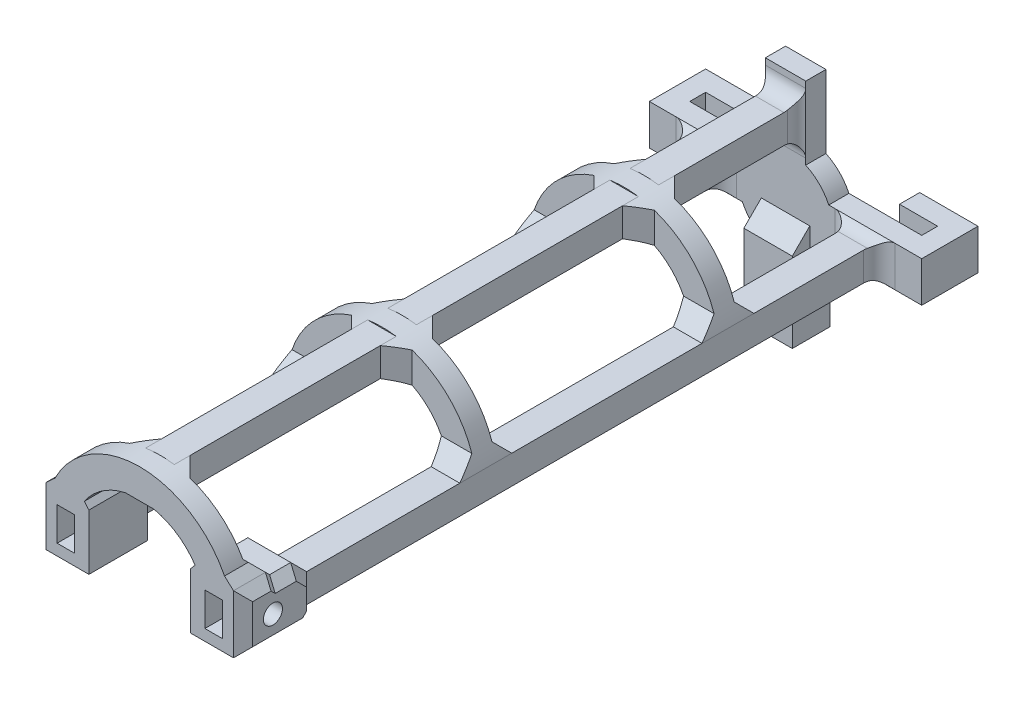
SolidWorks part; units mm, degrees
note: The reader was unsure of these and kept them because the rebuilt part matched: shared geometry of "Sketch11<2>", "Sketch11<3>", "Sketch15<2>", "Sketch14<2>".
ref_plane "Front Plane" through (0, 0, 0) normal (0, 0, 1) x (1, 0, 0)
ref_plane "Top Plane" through (0, 0, 0) normal (0, 1, 0) x (1, 0, 0)
ref_plane "Right Plane" through (0, 0, 0) normal (1, 0, 0) x (0, 0, -1)
sketch "Sketch1" plane through (0, 0, 0) normal (0, 0, 1) x (1, 0, 0)
  line L0 (-13.5896, -6.35) -> (-36.5, -6.35)
  line L1 (-6.35, 36.5) -> (6.35, 36.5)
  line L2 (-6.35, 36.5) -> (-6.35, 13.5896)
  line L3 (-7.62, -33) -> (7.62, -33)
  line L4 (6.35, 36.5) -> (6.35, 13.5896)
  line L5 (36.5, 6.35) -> (13.5896, 6.35)
  line L6 (36.5, 6.35) -> (36.5, -6.35)
  line L7 (36.5, -6.35) -> (13.5896, -6.35)
  line L8 (-36.5, 6.35) -> (-36.5, -6.35)
  line L9 (7.62, -12.9204) -> (7.62, -33)
  line L10 (-13.5896, 6.35) -> (-36.5, 6.35)
  line L11 (-7.62, -12.9204) -> (-7.62, -33)
  arc A0 (-13.5896, -6.35) -> (-7.62, -12.9204) centre (0, 0) ccw
  arc A1 (-6.35, 13.5896) -> (-13.5896, 6.35) centre (0, 0) ccw
  arc A2 (13.5896, 6.35) -> (6.35, 13.5896) centre (0, 0) ccw
  arc A3 (7.62, -12.9204) -> (13.5896, -6.35) centre (0, 0) ccw
  point P1 (6.35, -38.6284)
  point P11 (0, 36.5)
  point P13 (-36.5, 0)
  point P16 (6.3526, -42.9555)
  point P22 (9.9826, 34.5862)
  point P23 (-35.5946, -4.6384)
  dimension "D3" = 15
  dimension "D1" = 73
  dimension "D2" = 12.7
  dimension "D4" = 15.24
  dimension "D5" = 33
extrude "Boss-Extrude1" add sketch "Sketch1" along normal blind 6.35
sketch "Sketch5" plane through (7.62, 0, 0) normal (1, 0, 0) x (0, 0, -1)
  line L0 (-6.35, -2.325) -> (-11.85, -7.825)
  line L1 (-6.35, -33) -> (-11.85, -33)
  line L2 (-6.35, -33) -> (-6.35, -2.325)
  line L4 (-11.85, -33) -> (-11.85, -7.825)
  line L5 (0, -33) -> (0, -12.9204) construction
  point P7 (-11.85, -19.083)
  dimension "D1" = 135
  dimension "D2" = 11.85
  dimension "D3" = 25.175
extrude "Boss-Extrude2" add sketch "Sketch5" against normal up to surface (15.24 mm away) up to face at (-7.62, -22.9602, 3.175)
sketch "Sketch9" plane through (0, 6.35, 0) normal (0, 1, 0) x (1, 0, 0)
  line L0 (-36.5, -6.35) -> (-42.85, -6.35)
  line L1 (-42.85, -6.35) -> (-42.85, 11.35)
  line L2 (-42.85, 11.35) -> (-24.5, 11.35)
  line L9 (-36.5, 0) -> (-36.5, 5)
  line L10 (-36.5, 5) -> (-24.5, 5)
  line L11 (-24.5, 5) -> (-24.5, 11.35)
  line L12 (-36.5, 0) -> (-36.5, -6.35)
  line L14 (0, 0) -> (0, 11.35) construction
  line L15 (36.5, 0) -> (36.5, -6.35)
  line L16 (24.5, 5) -> (24.5, 11.35)
  line L17 (36.5, 5) -> (24.5, 5)
  line L18 (36.5, 0) -> (36.5, 5)
  line L19 (42.85, 11.35) -> (24.5, 11.35)
  line L20 (42.85, -6.35) -> (42.85, 11.35)
  line L21 (36.5, -6.35) -> (42.85, -6.35)
  dimension "D1" = 5
  dimension "D2" = 12
  dimension "D3" = 6.35
  dimension "D4" = 6.35
extrude "Boss-Extrude4" add sketch "Sketch9" against normal up to surface (12.7 mm away) up to face at (-25.0448, -6.35, 3.175)
sketch "Sketch6" plane through (0, -33, 0) normal (0, -1, 0) x (1, 0, 0)
  line L0 (-7.62, 11.85) -> (-7.62, 0) construction
  line L1 (-5.25, 8.675) -> (5.25, 8.675)
  line L2 (-5.25, 8.675) -> (-5.25, 3.175)
  line L3 (-5.25, 3.175) -> (5.25, 3.175)
  line L4 (5.25, 8.675) -> (5.25, 3.175)
  point P4 (0, 3.175)
  point P8 (-7.62, 5.925)
  point P9 (-5.25, 5.925)
  dimension "D1" = 10.5
  dimension "D2" = 5.5
extrude "Cut-Extrude1" cut sketch "Sketch6" against normal blind 22
chamfer "Chamfer2" distance 0.6 angle 45 4 edges at (-5.25, -22, 3.175) (-5.25, -22, 8.675) (5.25, -22, 8.675) (5.25, -22, 3.175)
sketch "Sketch7" plane through (0, 0, 6.35) normal (0, 0, 1) x (1, 0, 0)
  line L0 (0, 0) -> (0, 25) construction
  line L1 (-25, 0) -> (0, 0) construction
  line L2 (0, 0) -> (25, 0) construction
  line L4 (-29.5, -4.5) -> (-20.5, -4.5)
  line L5 (-29.5, -4.5) -> (-29.5, 4.5)
  line L6 (-29.5, 4.5) -> (-20.5, 4.5)
  line L7 (-20.5, -4.5) -> (-20.5, 4.5)
  line L8 (-29.5, -4.5) -> (-20.5, 4.5) construction
  line L9 (-29.5, 4.5) -> (-20.5, -4.5) construction
  line L10 (-4.5, 29.5) -> (4.5, 29.5)
  line L11 (-4.5, 29.5) -> (-4.5, 20.5)
  line L12 (-4.5, 20.5) -> (4.5, 20.5)
  line L13 (4.5, 29.5) -> (4.5, 20.5)
  line L14 (-4.5, 29.5) -> (4.5, 20.5) construction
  line L15 (-4.5, 20.5) -> (4.5, 29.5) construction
  line L16 (20.5, 4.5) -> (29.5, 4.5)
  line L17 (20.5, 4.5) -> (20.5, -4.5)
  line L18 (20.5, -4.5) -> (29.5, -4.5)
  line L19 (29.5, 4.5) -> (29.5, -4.5)
  line L20 (20.5, 4.5) -> (29.5, -4.5) construction
  line L21 (20.5, -4.5) -> (29.5, 4.5) construction
  dimension "D1" = 9
  dimension "D2" = 25
extrude "Boss-Extrude3" add sketch "Sketch7" along normal blind 203.2
fillet "Fillet1" radius 5 12 edges at (25, -4.5, 6.35) (-25, -4.5, 6.35) (-29.5, 0, 6.35) (-25, 4.5, 6.35) (-20.5, 0, 6.35) (20.5, 0, 6.35) (25, 4.5, 6.35) (29.5, 0, 6.35) (4.5, 25, 6.35) (0, 20.5, 6.35) (0, 29.5, 6.35) (-4.5, 25, 6.35)
sketch "Sketch11" plane through (0, 0, 209.55) normal (0, 0, 1) x (1, 0, 0)
  line L0 (-29.5, 4.5) -> (-20.5, 4.5)
  line L1 (-20.5, 4.5) -> (-29.5, 4.5) construction
  line L2 (29.5, 4.5) -> (20.5, 4.5)
  arc A0 (29.5, 4.5) -> (-29.5, 4.5) centre (0, 0) ccw
  arc A2 (20.5, 4.5) -> (-20.5, 4.5) centre (0, 0) ccw
extrude "Boss-Extrude6" add sketch "Sketch11" against normal blind 6.35 from offset 152.4 offset against normal yes
extrude "Boss-Extrude7" add sketch "Sketch11<2>" against normal blind 6.35 from offset 76.2 offset against normal yes
sketch "Sketch11<2>" plane through (0, 0, 209.55) normal (0, 0, 1) x (1, 0, 0) same geometry as "Sketch11"
extrude "Boss-Extrude8" add sketch "Sketch11<3>" against normal blind 6.35
sketch "Sketch11<3>" plane through (0, 0, 209.55) normal (0, 0, 1) x (1, 0, 0) same geometry as "Sketch11"
chamfer "Chamfer3" distance 5 angle 45 18 edges at (-25, 4.5, 57.15) (-25, 4.5, 50.8) (-25, 4.5, 133.35) (-25, 4.5, 127) (25, 4.5, 133.35) (25, 4.5, 127) (25, 4.5, 57.15) (25, 4.5, 50.8) (4.5, 25, 50.8) (-4.5, 25, 50.8) (-4.5, 25, 57.15) (4.5, 25, 57.15) (4.5, 25, 133.35) (-4.5, 25, 133.35) (-4.5, 25, 127) (4.5, 25, 127) (4.5, 25, 203.2) (-4.5, 25, 203.2)
sketch "Sketch13" plane through (0, 0, 209.55) normal (0, 0, 1) x (1, 0, 0)
  line L0 (20.5, -4.5) -> (29.5, -4.5) construction
  line L1 (-29.5, -7.5) -> (-16, -7.5)
  line L2 (-29.5, -7.5) -> (-29.5, 9.5)
  line L3 (-29.5, 9.5) -> (-16, 9.5)
  line L4 (-16, -7.5) -> (-16, 9.5)
  line L5 (16, 9.5) -> (29.5, 9.5)
  line L6 (16, 9.5) -> (16, -7.5)
  line L7 (16, -7.5) -> (29.5, -7.5)
  line L8 (29.5, 9.5) -> (29.5, -7.5)
  line L10 (-29.5, 4.5) -> (-29.5, -4.5) construction
  dimension "D2" = 17
  dimension "D3" = 16
  dimension "D4" = 16
  dimension "D5" = 3
extrude "Boss-Extrude9" add sketch "Sketch13" against normal blind 18
chamfer "Chamfer6" distance 5 angle 45 8 edges at (23.5018, 9.5, 203.2) (-23.5018, 9.5, 203.2) (-25, -4.5, 191.55) (-20.5, 0, 191.55) (-25, 4.5, 191.55) (25, -4.5, 191.55) (20.5, 0, 191.55) (25, 4.5, 191.55)
chamfer "Chamfer7" distance 3 angle 45 4 edges at (-28.2887, 9.5, 203.875) (-18.715, 9.5, 203.875) (18.715, 9.5, 203.875) (28.2887, 9.5, 203.875)
sketch "Sketch12" plane through (0, 0, 209.55) normal (0, 0, 1) x (1, 0, 0)
  line L1 (-26, 6.5) -> (-20.5, 6.5)
  line L2 (-26, 6.5) -> (-26, -4)
  line L3 (-26, -4) -> (-20.5, -4)
  line L4 (-20.5, 6.5) -> (-20.5, -4)
  line L5 (20.5, 6.5) -> (26, 6.5)
  line L6 (20.5, 6.5) -> (20.5, -4)
  line L7 (20.5, -4) -> (26, -4)
  line L8 (26, 6.5) -> (26, -4)
  dimension "D1" = 4
  dimension "D2" = 10.5
  dimension "D3" = 5.5
  dimension "D4" = 20.5
  dimension "D5" = 20.5
extrude "Cut-Extrude2" cut sketch "Sketch12" against normal blind 15.65
sketch "Sketch15" plane through (-29.5, 0, 0) normal (-1, 0, 0) x (0, 0, 1)
  line L0 (186.55, 4.5) -> (186.55, -4.5)
  line L14 (198.2, 9.5) -> (191.55, 9.5)
  line L15 (191.55, 9.5) -> (186.55, 4.5)
  line L16 (186.55, 4.5) -> (138.35, 4.5)
  line L17 (138.35, 4.5) -> (122, 4.5)
  line L18 (122, 4.5) -> (62.15, 4.5)
  line L19 (62.15, 4.5) -> (45.8, 4.5)
  line L20 (45.8, 4.5) -> (11.35, 4.5)
  line L21 (11.35, 4.5) -> (11.35, -4.5)
  line L22 (11.35, -4.5) -> (186.55, -4.5)
  line L23 (186.55, -4.5) -> (189.55, -7.5)
  line L24 (189.55, -7.5) -> (209.55, -7.5)
  line L25 (209.55, -7.5) -> (209.55, 10.8024)
  line L26 (209.55, 10.8024) -> (199.5024, 10.8024)
  line L27 (199.5024, 10.8024) -> (198.2, 9.5)
  line L28 (198.2, 9.5) -> (191.55, 9.5)
  line L29 (191.55, 9.5) -> (186.55, 4.5)
  line L37 (186.55, -4.5) -> (189.55, -7.5)
  line L38 (189.55, -7.5) -> (209.55, -7.5)
  line L39 (209.55, -7.5) -> (209.55, 10.8024)
  line L40 (209.55, 10.8024) -> (199.5024, 10.8024)
  line L41 (199.5024, 10.8024) -> (198.2, 9.5)
  dimension "D1" = 0
extrude "Boss-Extrude10" add sketch "Sketch15" along normal blind 3 draft 45
extrude "Boss-Extrude11" add sketch "Sketch15<2>" against normal blind 3 draft 45 from surface at -59
sketch "Sketch15<2>" plane through (-29.5, 0, 0) normal (-1, 0, 0) x (0, 0, 1) same geometry as "Sketch15"
sketch "Sketch14" plane through (-29.5, 0, 0) normal (-1, 0, 0) x (0, 0, 1)
  line L0 (209.55, 10.8024) -> (209.55, -7.5) construction
  line L1 (209.55, 6.5) -> (209.55, -4) construction
  circle A0 centre (200.15, 1.25) radius 3
  point P4 (0, 0)
  point P7 (209.55, 1.25)
  dimension "D1" = 6
  dimension "D2" = 9.4
extrude "Cut-Extrude3" cut sketch "Sketch14" against normal up to next (3.5 mm away) from surface at 3 starting at face at (-32.5, 2.4506, 196.9966)
extrude "Cut-Extrude4" cut sketch "Sketch14<2>" along normal up to next from surface
sketch "Sketch14<2>" plane through (-29.5, 0, 0) normal (-1, 0, 0) x (0, 0, 1) same geometry as "Sketch14"
